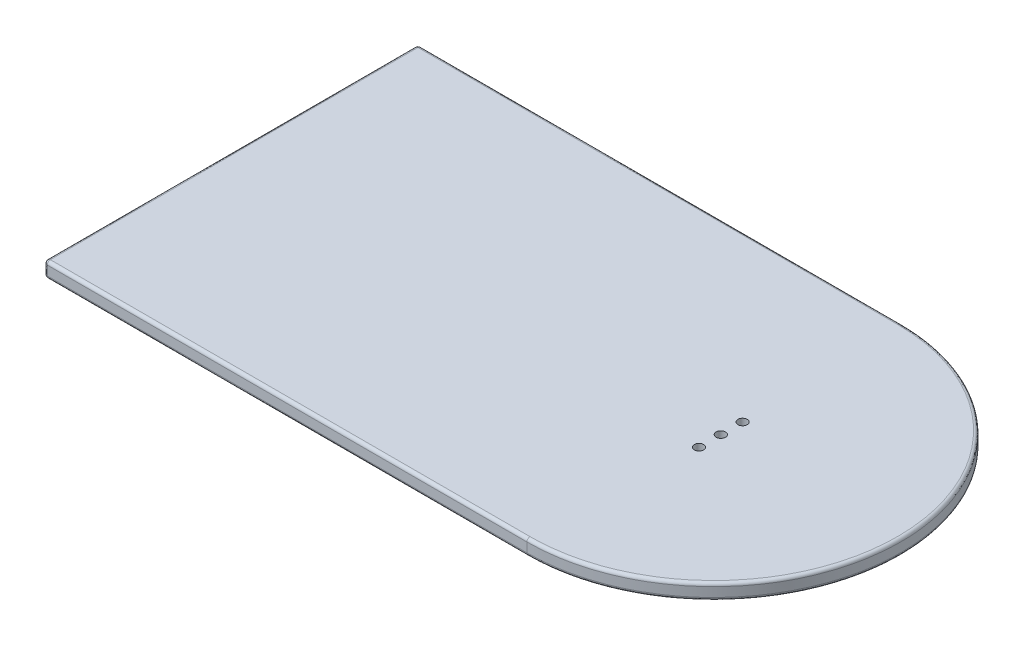
SolidWorks part; units mm, degrees
ref_plane "Front Plane" through (0, 0, 0) normal (0, 0, 1) x (1, 0, 0)
ref_plane "Top Plane" through (0, 0, 0) normal (0, 1, 0) x (1, 0, 0)
ref_plane "Right Plane" through (0, 0, 0) normal (1, 0, 0) x (0, 0, -1)
sketch "Sketch1" plane through (0, 0, 0) normal (0, 1, 0) x (1, 0, 0)
  line L1 (77.5, 60) -> (-77.5, 60)
  line L2 (77.5, 60) -> (77.5, -60)
  line L3 (77.5, -60) -> (-77.5, -60)
  line L4 (-77.5, 60) -> (-77.5, -60)
  line L5 (77.5, 60) -> (-77.5, -60) construction
  line L6 (77.5, -60) -> (-77.5, 60) construction
  arc A0 (77.5, -60) -> (77.5, 60) centre (77.5, 0) ccw
  point P0 (0, 0)
  dimension "D1" = 120
  dimension "D2" = 155
extrude "Boss-Extrude2" add sketch "Sketch1" along normal blind 5 contours L1 L4 L3 L2 | L2 A0 region at (0, 0, 0) region at (102.9648, 0, 0)
fillet "Fillet1" radius 1 10 edges at (-77.5, 2.5, -60) (-77.5, 2.5, 60) (-77.5, 0, 0) (0, 0, -60) (137.5, 0, 0) (0, 0, 60) (-77.5, 5, 0) (0, 5, -60) (137.5, 5, 0) (0, 5, 60) first distance on face at (-77.5, 2.5, 0) first distance on face at (15, 0, 0) first distance on face at (15, 5, 0)
hole_wizard "Ø3.0mm Dowel Hole2" positions "Sketch6" profile "Sketch7" hole size "Ø3.0" standard "ISO" end condition through all
sketch "Sketch6" plane through (0, 5, 0) normal (0, 1, 0) x (1, 0, 0)
  point P0 (79.7651, 0)
  point P2 (79.7651, -7)
  point P4 (79.7651, 7)
  point P12 (78.1914, 10.2397)
  point P13 (0, 0)
  point P14 (0, 0)
  point P15 (0, 0)
  point P16 (0, 0)
  dimension "D1" = 59
  dimension "D2" = 7
  dimension "D3" = 7
sketch "Sketch7" plane through (79.7651, 5, 0) normal (1, 0, 0) x (0, 0, 1)
  line L0 (0, 0) -> (0, 5.005)
  line L1 (0, 5.005) -> (1.5, 5.005)
  line L2 (1.5, 5.005) -> (1.5, 0)
  line L5 (1.5, 0) -> (0, 0)
  line L11 (0, -6.35) -> (0, 107.95) construction
  dimension "Thru Hole Dia." = 3
  dimension "Thru Hole Depth" = 5.005
